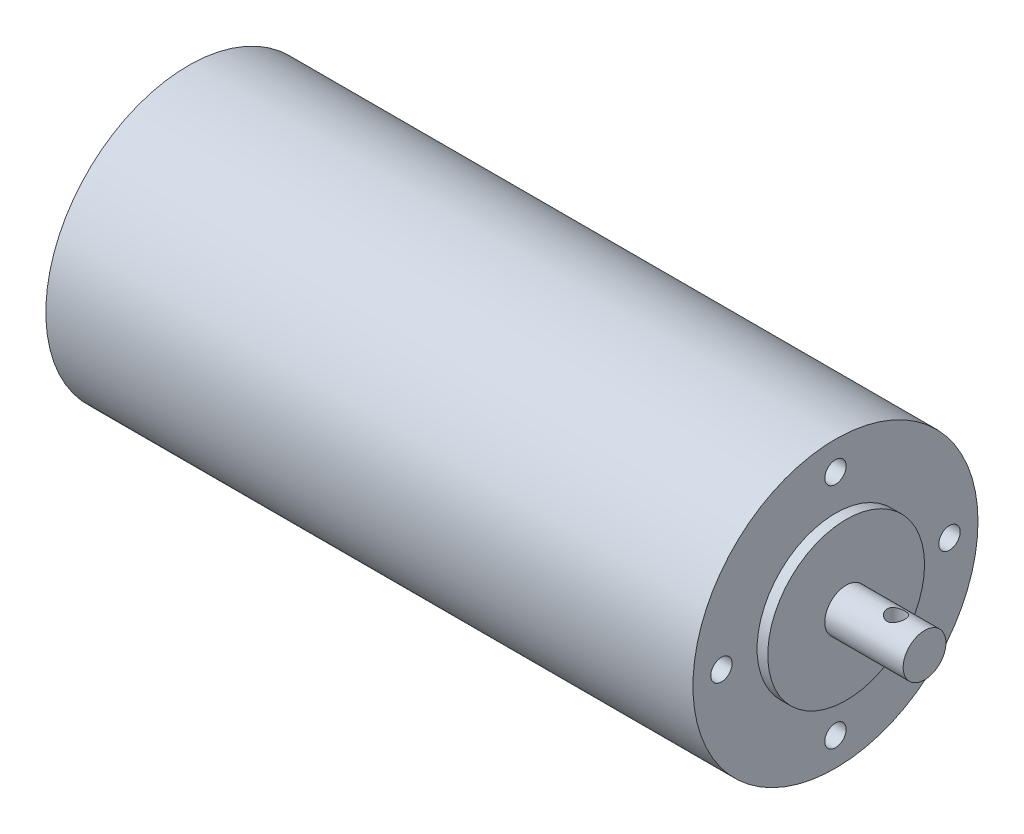
SolidWorks part; units mm, degrees
ref_plane "Front Plane" through (0, 0, 0) normal (0, 0, 1) x (1, 0, 0)
ref_plane "Top Plane" through (0, 0, 0) normal (0, 1, 0) x (1, 0, 0)
ref_plane "Right Plane" through (0, 0, 0) normal (1, 0, 0) x (0, 0, -1)
sketch "Sketch1" plane through (0, 0, 0) normal (1, 0, 0) x (0, 0, -1)
  circle A0 centre (0, 0) radius 20
  dimension "D1" = 40
extrude "Boss-Extrude1" add sketch "Sketch1" along normal blind 90.8
sketch "Sketch2" plane through (90.8, 0, 0) normal (1, 0, 0) x (0, 0, -1)
  circle A0 centre (0, 0) radius 11
  dimension "D1" = 22
extrude "Boss-Extrude2" add sketch "Sketch2" along normal blind 1.5
sketch "Sketch3" plane through (90.8, 0, 0) normal (1, 0, 0) x (0, 0, -1)
  circle A0 centre (0, 0) radius 16 construction
  circle A1 centre (0, 16) radius 1.5
  circle A2 centre (16, 0) radius 1.5
  circle A3 centre (0, -16) radius 1.5
  circle A4 centre (-16, 0) radius 1.5
  point P14 (0, 0)
  dimension "D1" = 32
  dimension "D2" = 3
  dimension "D4" = 16
  dimension "D5" = 16
  dimension "D3" = 4
extrude "Cut-Extrude1" cut sketch "Sketch3" against normal blind 3.2
sketch "Sketch4" plane through (92.3, 0, 0) normal (1, 0, 0) x (0, 0, -1)
  circle A0 centre (0, 0) radius 6.5
  dimension "D1" = 13
extrude "Cut-Extrude2" cut sketch "Sketch4" against normal blind 5
sketch "Sketch5" plane through (87.3, 0, 0) normal (1, 0, 0) x (0, 0, -1)
  circle A0 centre (0, 0) radius 3
  dimension "D1" = 6
extrude "Boss-Extrude3" add sketch "Sketch5" along normal blind 16
sketch "Sketch6" plane through (0, 0, 0) normal (0, 1, 0) x (1, 0, 0)
  line L0 (103.3, 0) -> (0, 0) construction
  line L1 (103.3, -3) -> (103.3, 3) construction
  circle A0 centre (99.3, 0) radius 1.25
  dimension "D1" = 2.5
  dimension "D2" = 4
extrude "Cut-Extrude3" cut sketch "Sketch6" against normal blind 10 and the other way blind 10
sketch "Sketch7" plane through (87.3, 0, 0) normal (1, 0, 0) x (0, 0, -1)
  circle A0 centre (0, 0) radius 6.5 construction
  circle A1 centre (0, 0) radius 6.5
extrude "Boss-Extrude4" add sketch "Sketch7" along normal up to surface (5 mm away) up to face at (92.3, 0, -6.5)
